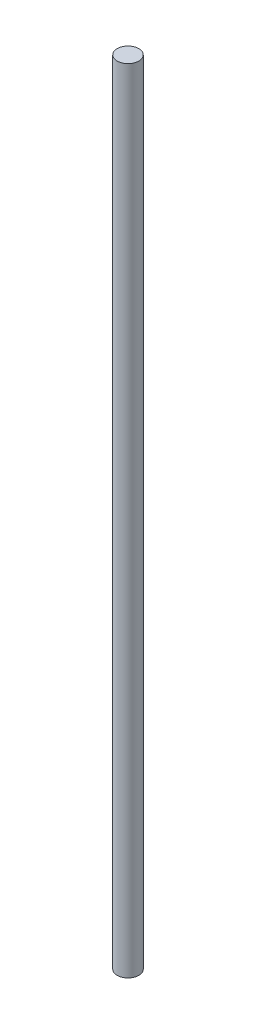
SolidWorks part; units mm, degrees
ref_plane "Front Plane" through (0, 0, 0) normal (0, 0, 1) x (1, 0, 0)
ref_plane "Top Plane" through (0, 0, 0) normal (0, 1, 0) x (1, 0, 0)
ref_plane "Right Plane" through (0, 0, 0) normal (1, 0, 0) x (0, 0, -1)
sketch "Sketch1" plane through (0, 0, 0) normal (0, 1, 0) x (1, 0, 0)
  circle A0 centre (0, 0) radius 4.7625
  dimension "D1" = 9.525
extrude "Boss-Extrude1" add sketch "Sketch1" along normal blind 349.25
equation "\"Lead_Screw_Diam\"= 0.375in"
equation "\"Mid_Coupler_Length\"= 12in"
equation "\"Lead_Screw_Length\"= \"Mid_Coupler_Length\" + 2*0.375in + 2*0.5in"
equation "\"D1@Sketch1\"=\"Lead_Screw_Diam\""
equation "\"D1@Boss-Extrude1\"=\"Lead_Screw_Length\""
